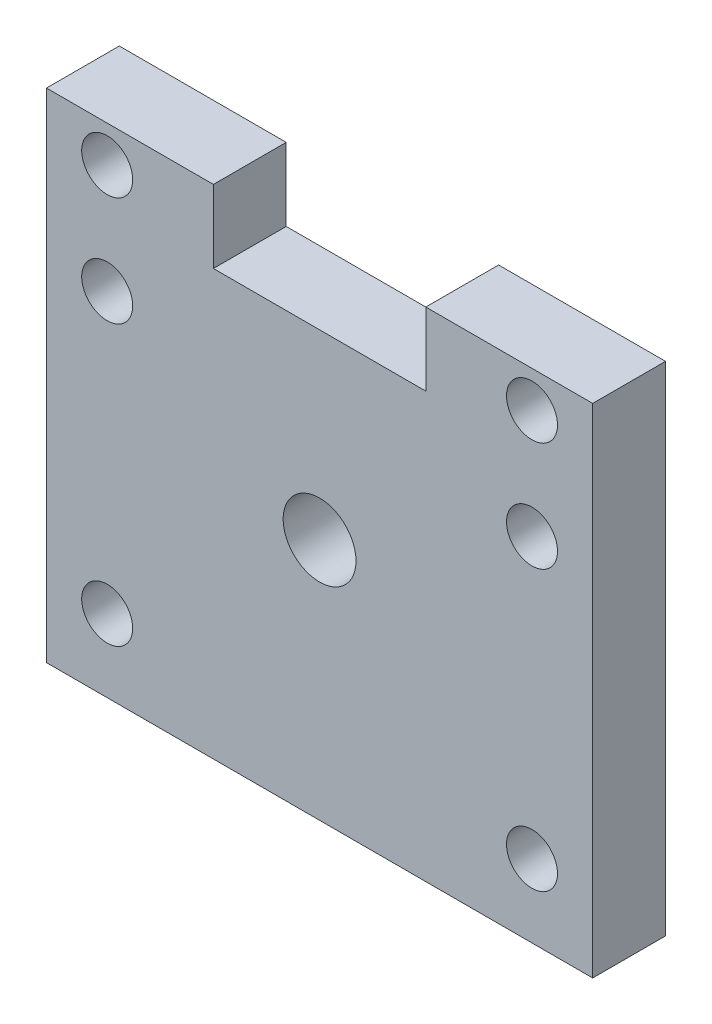
SolidWorks part; units mm, degrees
material "K110"
ref_plane "Front Plane" through (0, 0, 0) normal (0, 0, 1) x (1, 0, 0)
ref_plane "Top Plane" through (0, 0, 0) normal (0, 1, 0) x (1, 0, 0)
ref_plane "Right Plane" through (0, 0, 0) normal (1, 0, 0) x (0, 0, -1)
sketch "Sketch1" plane through (0, 0, 0) normal (0, 0, 1) x (1, 0, 0)
  line L1 (-45, -41) -> (45, -41)
  line L2 (-45, -41) -> (-45, 41)
  line L3 (-45, 41) -> (45, 41)
  line L4 (45, -41) -> (45, 41)
  line L5 (-45, -41) -> (45, 41) construction
  line L6 (-45, 41) -> (45, -41) construction
  point P0 (0, 0)
  dimension "D1" = 90
  dimension "D2" = 82
extrude "Boss-Extrude1" add sketch "Sketch1" along normal mid plane 12 contours L3 L4 L1 L2
hole_wizard "M8 Clearance Hole1" positions "Sketch5" profile "Sketch3" hole size "M8" standard "ISO" end condition through all
sketch "Sketch5" plane through (0, 0, 6) normal (0, 0, 1) x (1, 0, 0)
  point P0 (-35, 17)
  point P3 (35, 17)
  point P6 (35, -29)
  point P9 (-35, -29)
  point P13 (-35, 35)
  point P16 (35, 35)
sketch "Sketch3" plane through (-35, 17, 6) normal (1, 0, 0) x (0, -1, 0)
  line L0 (0, 0) -> (0, 12)
  line L1 (0, 12) -> (4.2, 12)
  line L2 (4.2, 12) -> (4.2, 0)
  line L5 (4.2, 0) -> (0, 0)
  line L11 (0, -6.35) -> (0, 107.95) construction
  dimension "Thru Hole Dia." = 8.4
  dimension "Thru Hole Depth" = 12
sketch "Sketch6" plane through (0, 41, 0) normal (0, 1, 0) x (1, 0, 0)
  line L0 (-45, -6) -> (45, -6) construction
  line L1 (17.5, -6) -> (-17.5, -6)
  line L2 (17.5, -6) -> (17.5, 6)
  line L3 (17.5, 6) -> (-17.5, 6)
  line L4 (-17.5, -6) -> (-17.5, 6)
  line L5 (-45, 6) -> (45, 6) construction
  line L6 (0, -6) -> (0, 6) construction
  dimension "D1" = 35
extrude "Cut-Extrude1" cut sketch "Sketch6" against normal blind 12 and the other way through all
hole_wizard "Ø12.0 (12) Diameter Hole1" positions "Sketch9" profile "Sketch8" hole size "Ø12.0" standard "ISO" end condition through all
sketch "Sketch9" plane through (0, 0, 6) normal (0, 0, 1) x (1, 0, 0)
  point P2 (0, -1)
sketch "Sketch8" plane through (0, -1, 6) normal (1, 0, 0) x (0, -1, 0)
  line L0 (0, 0) -> (0, 12)
  line L1 (0, 12) -> (6, 12)
  line L2 (6, 12) -> (6, 0)
  line L5 (6, 0) -> (0, 0)
  line L11 (0, -6.35) -> (0, 107.95) construction
  dimension "Thru Hole Dia." = 12
  dimension "Thru Hole Depth" = 12
